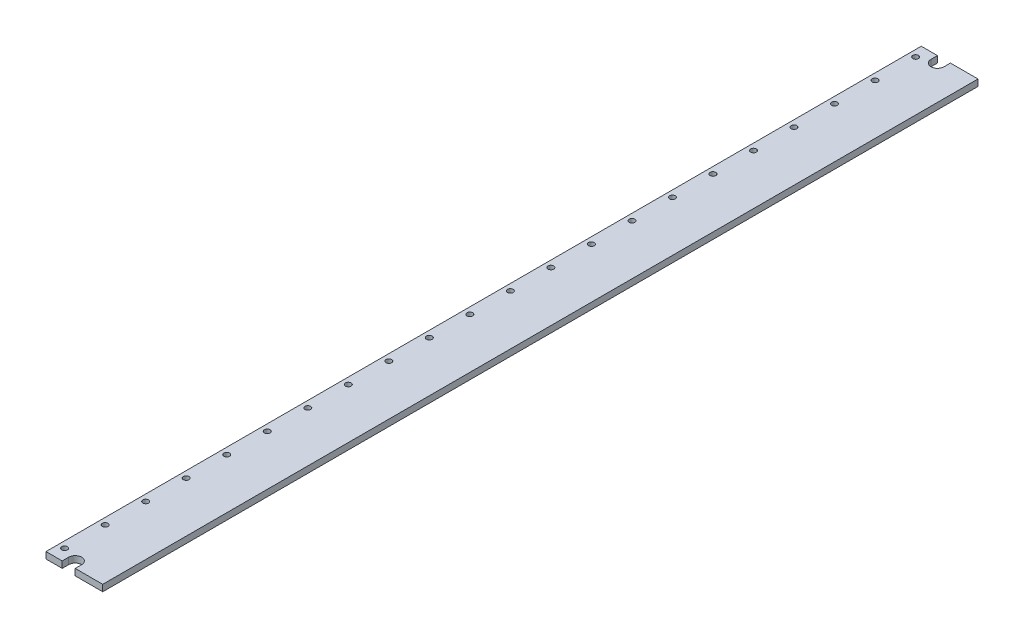
SolidWorks part; units mm, degrees
ref_plane "Front Plane" through (0, 0, 0) normal (0, 0, 1) x (1, 0, 0)
ref_plane "Top Plane" through (0, 0, 0) normal (0, 1, 0) x (1, 0, 0)
ref_plane "Right Plane" through (0, 0, 0) normal (1, 0, 0) x (0, 0, -1)
sketch "Sketch1" plane through (0, 0, 0) normal (0, 0, 1) x (1, 0, 0)
  line L0 (17.5, 2) -> (-17.5, 2)
  line L1 (-17.5, -2) -> (17.5, -2)
  line L4 (17.5, -2) -> (17.5, 2)
  line L5 (-17.5, -2) -> (17.5, 2) construction
  line L9 (-17.5, -2) -> (-17.5, 2)
  point P0 (0, 0)
  dimension "D1" = 4
extrude "Boss-Extrude2" add sketch "Sketch1" along normal blind 540
sketch "Sketch2" plane through (0, 2, 0) normal (0, 1, 0) x (1, 0, 0)
  line L2 (17.5, 0) -> (-17.5, 0) construction
  line L3 (-17.5, -540) -> (-17.5, 0) construction
  circle A0 centre (-13.5, -7.5) radius 1.75
  dimension "D1" = 3.5
  dimension "D2" = 7.5
  dimension "D3" = 4
extrude "Cut-Extrude1" cut sketch "Sketch2" against normal through all
pattern_linear "LPattern1" count 22 spacing 25 along (0, 0, 1) of "Cut-Extrude1"
sketch "Sketch3" plane through (0, 2, 0) normal (0, 1, 0) x (1, 0, 0)
  line L0 (-7.5, 0) -> (-7.5, -4)
  line L1 (17.5, 0) -> (-17.5, 0) construction
  line L2 (0.5, 0) -> (0.5, -4)
  line L3 (-17.5, -540) -> (-17.5, 0) construction
  line L4 (-7.5, 0) -> (0.5, 0)
  line L5 (-7.5, -540) -> (-7.5, -536)
  line L6 (17.5, -540) -> (-17.5, -540) construction
  line L7 (0.5, -540) -> (0.5, -536)
  line L8 (-7.5, -540) -> (0.5, -540)
  arc A0 (0.5, -4) -> (-7.5, -4) centre (-3.5, -4) cw
  arc A1 (-7.5, -536) -> (0.5, -536) centre (-3.5, -536) cw
  dimension "D1" = 8
  dimension "D2" = 14
  dimension "D3" = 4
  dimension "D4" = 4
extrude "Cut-Extrude2" cut sketch "Sketch3" against normal up to next
